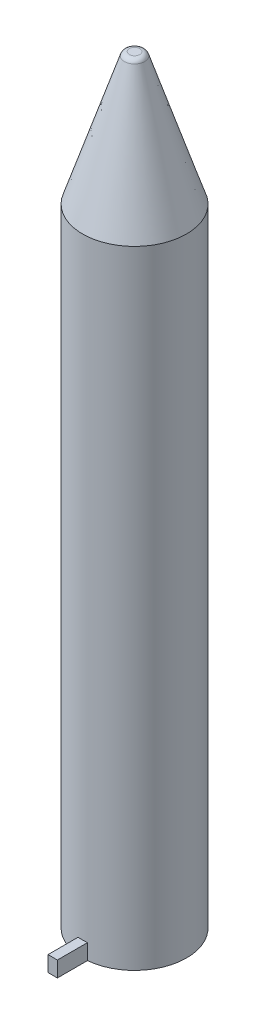
SolidWorks part; units mm, degrees
ref_plane "Front Plane" through (0, 0, 0) normal (0, 0, 1) x (1, 0, 0)
ref_plane "Top Plane" through (0, 0, 0) normal (0, 1, 0) x (1, 0, 0)
ref_plane "Right Plane" through (0, 0, 0) normal (1, 0, 0) x (0, 0, -1)
sketch "Sketch1" plane through (0, 0, 0) normal (0, 1, 0) x (1, 0, 0)
  circle A0 centre (0, 0) radius 10
  dimension "D1" = 20
extrude "Boss-Extrude1" add sketch "Sketch1" along normal blind 120.65
sketch "Sketch2" plane through (0, 0, 0) normal (0, 0, 1) x (1, 0, 0)
  line L8 (0, 120.65) -> (0, 146.05)
  line L9 (10, 120.65) -> (-10, 120.65) construction
  line L10 (1.9508, 145.3597) -> (10, 120.65)
  line L11 (10, 120.65) -> (0, 120.65)
  line L12 (1, 146.05) -> (0, 146.05)
  arc A3 (1, 146.05) -> (1.9508, 145.3597) centre (1, 145.05) cw
  dimension "D2" = 25.4
  dimension "D1" = 1
revolve "Revolve1" add sketch "Sketch2" angle 360 about L8
sketch "Sketch3" plane through (0, 0, 0) normal (0, -1, 0) x (1, 0, 0)
  line L1 (-0.9, 15.75) -> (0.9, 15.75)
  line L2 (-0.9, 15.75) -> (-0.9, 9.3548)
  line L4 (0.9, 15.75) -> (0.9, 9.3548)
  arc A0 (0.9, 9.3548) -> (-0.9, 9.3548) centre (0, 0) ccw
  dimension "D1" = 0.9
  dimension "D3" = 15.75
extrude "Boss-Extrude2" add sketch "Sketch3" against normal blind 3
sketch "Sketch4" plane through (0, 0, 0) normal (0, -1, 0) x (1, 0, 0)
  circle A0 centre (0, 0) radius 8
  dimension "D1" = 16
extrude "Cut-Extrude1" cut sketch "Sketch4" against normal blind 2.54
